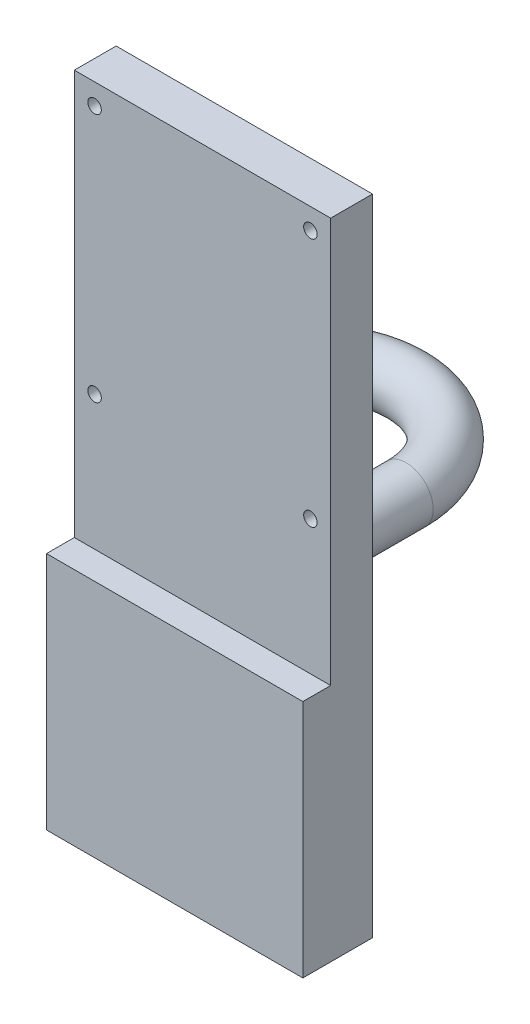
SolidWorks part; units mm, degrees
ref_plane "Plan de face" through (0, 0, 0) normal (0, 0, 1) x (1, 0, 0)
ref_plane "Plan de dessus" through (0, 0, 0) normal (0, 1, 0) x (1, 0, 0)
ref_plane "Plan de droite" through (0, 0, 0) normal (1, 0, 0) x (0, 0, -1)
sketch "Esquisse1" plane through (0, 0, 0) normal (0, 0, 1) x (1, 0, 0)
  line L1 (0, 0) -> (190, 0)
  line L2 (0, 0) -> (0, 300)
  line L3 (0, 300) -> (190, 300)
  line L4 (190, 0) -> (190, 300)
  dimension "D1" = 190
  dimension "D2" = 300
extrude "Boss.-Extru.1" add sketch "Esquisse1" along normal blind 31
sketch "Esquisse2" plane through (0, 0, 0) normal (0, 0, -1) x (-1, 0, 0)
  line L0 (-190, 300) -> (0, 300) construction
  line L3 (-190, 0) -> (-190, 300) construction
  line L4 (0, 300) -> (0, 0) construction
  line L5 (-1232.0432, 99.5) -> (48767.9568, 99.5) construction
  circle A0 centre (-175, 284.5) radius 5
  circle A1 centre (-15, 284.5) radius 5
  circle A2 centre (-175, 99.5) radius 5
  circle A3 centre (-15, 99.5) radius 5
  dimension "D1" = 10
  dimension "D4" = 10
  dimension "D8" = 10
  dimension "D9" = 10
  dimension "D2" = 15.5
  dimension "D3" = 15
  dimension "D5" = 15
  dimension "D6" = 15.5
  dimension "D7" = 200.5
  dimension "D10" = 15
  dimension "D11" = 15
extrude "Enlèv. mat.-Extru.1" cut sketch "Esquisse2" against normal through all
sketch "Esquisse3" plane through (0, 0, 0) normal (0, -1, 0) x (1, 0, 0)
  line L1 (0, 0) -> (190, 0)
  line L2 (0, 0) -> (0, 51.62)
  line L3 (0, 51.62) -> (190, 51.62)
  line L4 (190, 0) -> (190, 51.62)
  dimension "D1" = 190
  dimension "D2" = 51.62
extrude "Boss.-Extru.2" add sketch "Esquisse3" along normal blind 177.45
sketch "Esquisse4" plane through (0, 0, 0) normal (0, 0, -1) x (-1, 0, 0)
  line L0 (-190, -177.45) -> (0, 300) construction
  line L1 (-190, 300) -> (0, -177.45) construction
  line L3 (-95, -938.725) -> (-95, 49061.275) construction
  line L4 (-190, 300) -> (0, 300) construction
  circle A1 centre (-165, 70) radius 20
  point P11 (-95, 61.275)
  dimension "D1" = 70
  dimension "D3" = 40
  dimension "D2" = 230
extrude "Boss.-Extru.3" add sketch "Esquisse4" along normal blind 50 contours A1
ref_plane "Plan1" through (95, 0, 0) normal (1, 0, 0) x (0, 0, -1)
mirror "Symétrie1" about plane through (95, 0, 0) normal (1, 0, 0) of "Boss.-Extru.3"
ref_plane "Plan2" through (0, 0, -50) normal (0, 0, -1) x (-1, 0, 0)
ref_axis "Axe1" through (95, -201.3225, -50) along (0, 1, 0)
sketch "Esquisse6" plane through (0, 0, -50) normal (0, 0, -1) x (-1, 0, 0)
  circle A0 centre (-165, 70) radius 20
  dimension "D1" = 40
revolve "Révolution1" add sketch "Esquisse6" angle 180 about axis through (95, -201.3225, -50) along (0, 1, 0)
ref_plane "Plan3" through (0, 192, 0) normal (0, 1, 0) x (1, 0, 0)
equation "\"D7@Esquisse2\"=216-15.5"
equation "\"D2@Esquisse3\"=31+20.62"
